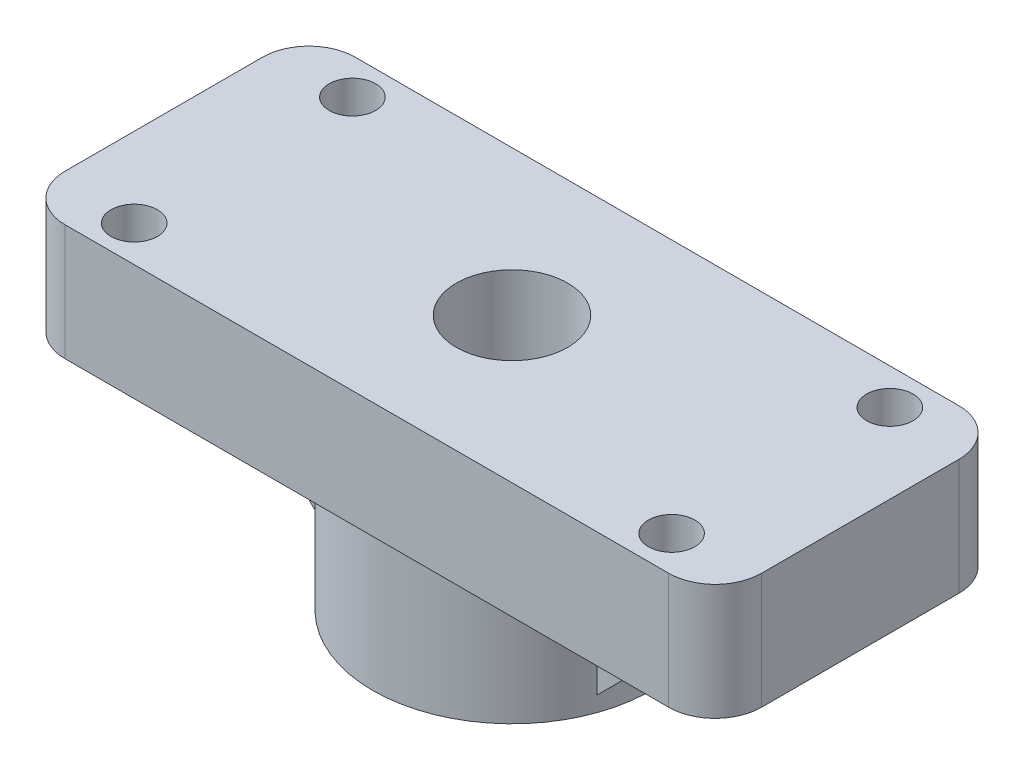
SolidWorks part; units mm, degrees
ref_plane "Front Plane" through (0, 0, 0) normal (0, 0, 1) x (1, 0, 0)
ref_plane "Top Plane" through (0, 0, 0) normal (0, 1, 0) x (1, 0, 0)
ref_plane "Right Plane" through (0, 0, 0) normal (1, 0, 0) x (0, 0, -1)
sketch "Sketch1" plane through (0, 0, 0) normal (0, 1, 0) x (1, 0, 0)
  line L1 (-30, 12.5) -> (30, 12.5)
  line L2 (-30, 12.5) -> (-30, -12.5)
  line L3 (-30, -12.5) -> (30, -12.5)
  line L4 (30, 12.5) -> (30, -12.5)
  point P4 (0, 12.5)
  point P6 (-30, 0)
  dimension "D1" = 25
  dimension "D2" = 60
extrude "Base" add sketch "Sketch1" along normal blind 10
sketch "Sketch2" plane through (0, 0, 0) normal (0, 0, 1) x (1, 0, 0)
  line L0 (0, 0) -> (0, -20.6179) construction
  line L1 (-4.8, 0) -> (-4.8, -7)
  line L2 (-30, 0) -> (30, 0) construction
  line L3 (-4.8, -7) -> (-4.5, -7)
  line L4 (-4.5, -7) -> (-4.5, -12)
  line L5 (-4.5, -12) -> (-12, -12)
  line L6 (-12, -12) -> (-12, 0)
  line L7 (-12, 0) -> (-4.8, 0)
  dimension "D1" = 12
  dimension "D2" = 4.8
  dimension "D3" = 4.5
  dimension "D4" = 12
  dimension "D5" = 7
revolve "Pen Catch" add sketch "Sketch2" angle 360 about L0
sketch "Sketch5" plane through (0, 10, 0) normal (0, 1, 0) x (1, 0, 0)
  circle A0 centre (0, 0) radius 4.8
  dimension "D1" = 9.6
extrude "Pen Hole" cut sketch "Sketch5" against normal up to next
sketch "Sketch4" plane through (0, 0, 0) normal (0, 0, 1) x (1, 0, 0)
  line L0 (-22, 0) -> (-10, 0)
  line L1 (-30, 0) -> (30, 0) construction
  line L2 (-10, 0) -> (-10, -12)
  line L3 (-10, -12) -> (-22, 0)
  line L4 (0, 0) -> (0, -27.3362) construction
  line L5 (-12, 0) -> (-12, -12) construction
  line L6 (10, -12) -> (22, 0)
  line L7 (10, 0) -> (10, -12)
  line L8 (22, 0) -> (10, 0)
  dimension "D1" = 45
  dimension "D2" = 10
  dimension "D3" = 12
extrude "Stab Fins" add sketch "Sketch4" along normal blind 4 and the other way blind 4
fillet "Base Dec" radius 4 4 edges at (-30, 5, -12.5) (30, 5, 12.5) (30, 5, -12.5) (-30, 5, 12.5)
sketch "Sketch8" plane through (0, 10, 0) normal (0, 1, 0) x (1, 0, 0)
  circle A0 centre (23.15, 9.4) radius 2
  circle A1 centre (23.15, -9.4) radius 2
  circle A2 centre (-23.15, 9.4) radius 2
  circle A3 centre (-23.15, -9.4) radius 2
  circle A4 centre (23.15, 9.4) radius 2 construction
  circle A5 centre (23.15, -9.4) radius 2 construction
  circle A6 centre (-23.15, -9.4) radius 2 construction
  circle A7 centre (-23.15, 9.4) radius 2 construction
extrude "Cut-Extrude2" cut sketch "Sketch8" against normal through all
